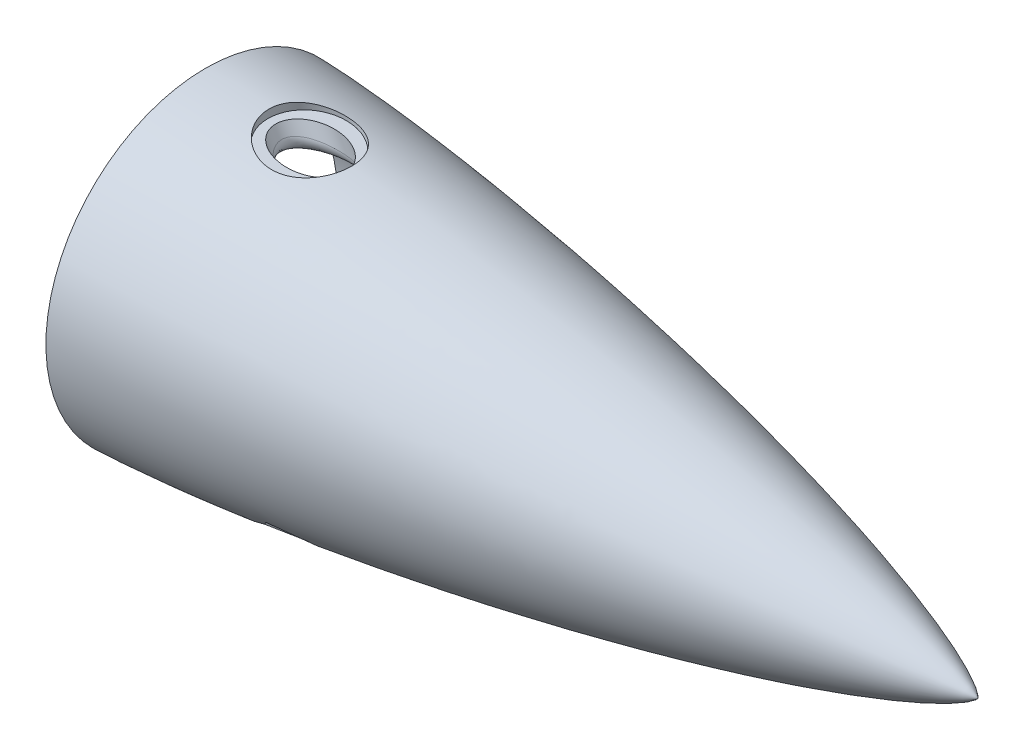
SolidWorks part; units mm, degrees
material "Plain Carbon Steel"
ref_plane "Front Plane" through (0, 0, 0) normal (0, 0, 1) x (1, 0, 0)
ref_plane "Top Plane" through (0, 0, 0) normal (0, 1, 0) x (1, 0, 0)
ref_plane "Right Plane" through (0, 0, 0) normal (1, 0, 0) x (0, 0, -1)
ref_axis "Axis1" through (444.767, 0, 0) along (-1, 0, 0)
sketch "Sketch10" plane through (0, 0, 0) normal (0, 0, 1) x (1, 0, 0)
  line L1 (-0.5188, 0) -> (486.9547, 0) construction
  line L2 (5.3953, 74.55) -> (5.3953, 64.55)
  line L3 (5.3953, 74.55) -> (0.3953, 74.55)
  line L4 (409.4812, 0) -> (389.4812, 0)
  line L7 (0.3953, 74.55) -> (0.3953, 84.55)
  line L8 (5.3953, 64.55) -> (123.5873, 64.55)
  line L9 (444.767, 0) -> (-98.162, 0) construction
  spline S0 degree 4 poles (409.4812, 0) (409.4788, 0.0135) (409.4718, 0.0399) (409.45, 0.0903) (409.4052, 0.1736) (409.3386, 0.2747) (409.2332, 0.4144) (409.0715, 0.6026) (408.8144, 0.8684) (408.376, 1.2687) (407.6237, 1.874) (406.3009, 2.8069) (403.9508, 4.2541) (399.8003, 6.4739) (392.937, 9.6599) (381.0889, 14.4581) (364.0279, 20.4397) (342.5658, 27.076) (317.7374, 33.9485) (292.1491, 40.4025) (266.444, 46.3727) (240.6453, 51.9227) (214.7673, 57.0897) (188.82, 61.8964) (166.0615, 65.7958) (146.5183, 68.9193) (130.2092, 71.3728) (117.1484, 73.2437) (104.0744, 75.0198) (92.6232, 76.4872) (82.7998, 77.6794) (74.6082, 78.627) (68.0516, 79.3563) (61.4918, 80.0556) (54.9286, 80.7233) (48.3622, 81.3575) (41.7923, 81.956) (36.0408, 82.4459) (31.1087, 82.8394) (26.9972, 83.1482) (23.7071, 83.3831) (20.0917, 83.6266) (16.7244, 83.837) (13.6055, 84.0163) (10.7352, 84.1667) (8.4384, 84.2771) (6.1411, 84.3768) (4.1305, 84.4519) (2.4068, 84.5068) (1.2575, 84.5344) (0.6827, 84.5468) (0.3953, 84.55) knots 0 0 0 0 0 0.00013 0.00026 0.00052 0.0009 0.00128 0.001925 0.002882 0.004418 0.006927 0.011111 0.018279 0.030673 0.051704 0.083102 0.139909 0.202703 0.265496 0.32829 0.391083 0.453877 0.516671 0.579464 0.642258 0.673655 0.705051 0.736448 0.767845 0.799242 0.81494 0.830639 0.846337 0.862036 0.877734 0.893432 0.909131 0.924829 0.932678 0.940527 0.948377 0.956226 0.967169 0.972641 0.978113 0.983585 0.989056 0.994528 0.997264 1 1 1 1 1 construction
  spline S1 degree 4 poles (409.4812, 0) (409.4788, 0.0135) (409.4718, 0.0399) (409.45, 0.0903) (409.4052, 0.1736) (409.3386, 0.2747) (409.2332, 0.4144) (409.0715, 0.6026) (408.8144, 0.8684) (408.376, 1.2687) (407.6237, 1.874) (406.3009, 2.8069) (403.9508, 4.2541) (399.8003, 6.4739) (392.937, 9.6599) (381.0889, 14.4581) (364.0279, 20.4397) (342.5658, 27.076) (317.7374, 33.9485) (292.1491, 40.4025) (266.444, 46.3727) (240.6453, 51.9227) (214.7673, 57.0897) (188.82, 61.8964) (166.0615, 65.7958) (146.5183, 68.9193) (130.2092, 71.3728) (117.1484, 73.2437) (104.0744, 75.0198) (92.6232, 76.4872) (82.7998, 77.6794) (74.6082, 78.627) (68.0516, 79.3563) (61.4918, 80.0556) (54.9286, 80.7233) (48.3622, 81.3575) (41.7923, 81.956) (36.0408, 82.4459) (31.1087, 82.8394) (26.9972, 83.1482) (23.7071, 83.3831) (20.0917, 83.6266) (16.7244, 83.837) (13.6055, 84.0163) (10.7352, 84.1667) (8.4384, 84.2771) (6.1411, 84.3768) (4.1305, 84.4519) (2.4068, 84.5068) (1.2575, 84.5344) (0.6827, 84.5468) (0.3953, 84.55) knots 0 0 0 0 0 0.00013 0.00026 0.00052 0.0009 0.00128 0.001925 0.002882 0.004418 0.006927 0.011111 0.018279 0.030673 0.051704 0.083102 0.139909 0.202703 0.265496 0.32829 0.391083 0.453877 0.516671 0.579464 0.642258 0.673655 0.705051 0.736448 0.767845 0.799242 0.81494 0.830639 0.846337 0.862036 0.877734 0.893432 0.909131 0.924829 0.932678 0.940527 0.948377 0.956226 0.967169 0.972641 0.978113 0.983585 0.989056 0.994528 0.997264 1 1 1 1 1
  spline S2 degree 4 poles (389.4812, 0) (389.479, 0.0123) (389.4725, 0.0363) (389.4525, 0.0822) (389.4122, 0.157) (389.353, 0.247) (389.2599, 0.3709) (389.1165, 0.539) (388.8864, 0.7783) (388.4926, 1.1395) (387.8141, 1.6869) (386.6231, 2.5278) (384.5051, 3.8315) (380.7852, 5.8157) (374.6858, 8.6351) (364.2129, 12.8526) (349.1803, 18.0828) (330.2962, 23.8619) (308.4491, 29.8289) (285.9329, 35.4155) (263.3136, 40.5677) (240.6118, 45.3419) (217.8404, 49.7716) (195.0084, 53.8768) (174.9827, 57.1927) (157.7866, 59.8376) (143.4365, 61.9069) (131.9448, 63.4795) (120.4418, 64.9665) (110.3667, 66.1893) (101.7241, 67.1782) (94.5172, 67.9608) (88.749, 68.5609) (82.9779, 69.1338) (77.2041, 69.6781) (71.4276, 70.1921) (65.6482, 70.6738) (60.5888, 71.0647) (56.2504, 71.3757) (52.6339, 71.6175) (49.74, 71.7999) (46.5831, 71.9858) (43.163, 72.1699) (39.9727, 72.3219) (37.0124, 72.4428) (34.5449, 72.5278) (32.8173, 72.5768) (31.3363, 72.6106) (30.3488, 72.6252) (29.8551, 72.6313) (29.6082, 72.6318) knots 0 0 0 0 0 0.000135 0.00027 0.00054 0.00092 0.001299 0.001947 0.002931 0.004512 0.007081 0.01138 0.018708 0.031424 0.052705 0.084103 0.14091 0.203703 0.266497 0.329291 0.392084 0.454878 0.517672 0.580465 0.643259 0.674656 0.706052 0.737449 0.768846 0.800243 0.815941 0.831639 0.847338 0.863036 0.878735 0.894433 0.910132 0.92583 0.933679 0.941528 0.949378 0.957227 0.96792 0.978613 0.98396 0.989307 0.994653 0.997327 1 1 1 1 1 construction
  spline S3 degree 4 poles (389.4812, 0) (389.479, 0.0123) (389.4725, 0.0363) (389.4525, 0.0822) (389.4122, 0.157) (389.353, 0.247) (389.2599, 0.3709) (389.1165, 0.539) (388.8864, 0.7783) (388.4926, 1.1395) (387.8141, 1.6869) (386.6231, 2.5278) (384.5051, 3.8315) (380.7852, 5.8157) (374.6858, 8.6351) (364.2129, 12.8526) (349.1803, 18.0828) (330.2962, 23.8619) (308.4491, 29.8289) (285.9329, 35.4155) (263.3136, 40.5677) (240.6118, 45.3419) (217.8404, 49.7716) (195.0084, 53.8768) (174.9827, 57.1927) (157.7866, 59.8376) (143.4365, 61.9069) (134.1672, 63.1754) (127.7661, 64.0153) (124.2387, 64.467) (123.5873, 64.55) knots 0 0 0 0 0 0.000135 0.00027 0.00054 0.00092 0.001299 0.001947 0.002931 0.004512 0.007081 0.01138 0.018708 0.031424 0.052705 0.084103 0.14091 0.203703 0.266497 0.329291 0.392084 0.454878 0.517672 0.580465 0.643259 0.674656 0.706052 0.737449 0.744559 0.744559 0.744559 0.744559 0.744559
  dimension "D1" = 84.55
  dimension "D3" = 410
  dimension "D5" = 390
  dimension "D7" = 20
  dimension "D8" = 118.192
  dimension "D2" = 10
  dimension "D4" = 5
revolve "Revolve1" add sketch "Sketch10" angle 360 about axis through (444.767, 0, 0) along (-1, 0, 0)
ref_plane "Plane3" through (0, 82.55, 0) normal (0, 1, 0) x (1, 0, 0)
sketch "Sketch20" plane through (0, 82.55, 0) normal (0, 1, 0) x (1, 0, 0)
  line L0 (444.767, 0) -> (-98.162, 0) construction
  line L1 (24.7702, 25) -> (64.7702, 25)
  line L2 (24.7702, 25) -> (24.7702, -15)
  line L3 (24.7702, -15) -> (64.7702, -15)
  line L4 (64.7702, 25) -> (64.7702, -15)
  line L5 (24.7702, 25) -> (64.7702, -15) construction
  line L6 (24.7702, -15) -> (64.7702, 25) construction
  point P4 (44.7702, 5)
  dimension "D1" = 40
  dimension "D2" = 15
  dimension "D3" = 40
extrude "Cut-Extrude3" [suppressed] cut sketch "Sketch20" along normal blind 12
sketch "Sketch22" plane through (0, 82.55, 0) normal (0, 1, 0) x (1, 0, 0)
  circle A0 centre (32, 6) radius 7.5
  dimension "D1" = 15
extrude "Cut-Extrude4" [suppressed] cut sketch "Sketch22" along normal through all
sketch "Sketch24" plane through (0, 82.55, 0) normal (0, 1, 0) x (1, 0, 0)
  line L0 (38.1988, 66.2764) -> (38.1988, 16.8548) construction
ref_plane "Plane4" through (-26.1955, 45.3719, 0) normal (-0.5, 0.866, 0) x (0, 0, 1)
sketch "Sketch26" plane through (-26.1955, 45.3719, 0) normal (-0.5, 0.866, 0) x (0, 0, 1)
  line L1 (-66.2764, 74.3561) -> (-16.8548, 74.3561) construction
  circle A0 centre (0, 86.3561) radius 15
  dimension "D1" = 12
extrude "Cut-Extrude5" cut sketch "Sketch26" against normal blind 50
ref_plane "Plane5" through (8.9989, 85.619, 0) normal (0.1045, 0.9945, 0) x (0, 0, 1)
sketch "Sketch30" plane through (8.9989, 85.619, 0) normal (0.1045, 0.9945, 0) x (0, 0, 1)
  line L0 (0, 442.3305) -> (0, -97.6242) construction
  circle A0 centre (0, 47.1511) radius 22
extrude "Cut-Extrude10" cut sketch "Sketch30" against normal blind 5
fillet "Fillet1" radius 5 1 edges at (79.2639, 64.4372, 3.8138)
equation "\"TubeDiameter\"= 6.500in"
equation "\"D1@Sketch10\"=\"TubeDiameter\"/2mm+2mm"
equation "\"D1@Plane3\"=\"TubeDiameter\"/2mm"
